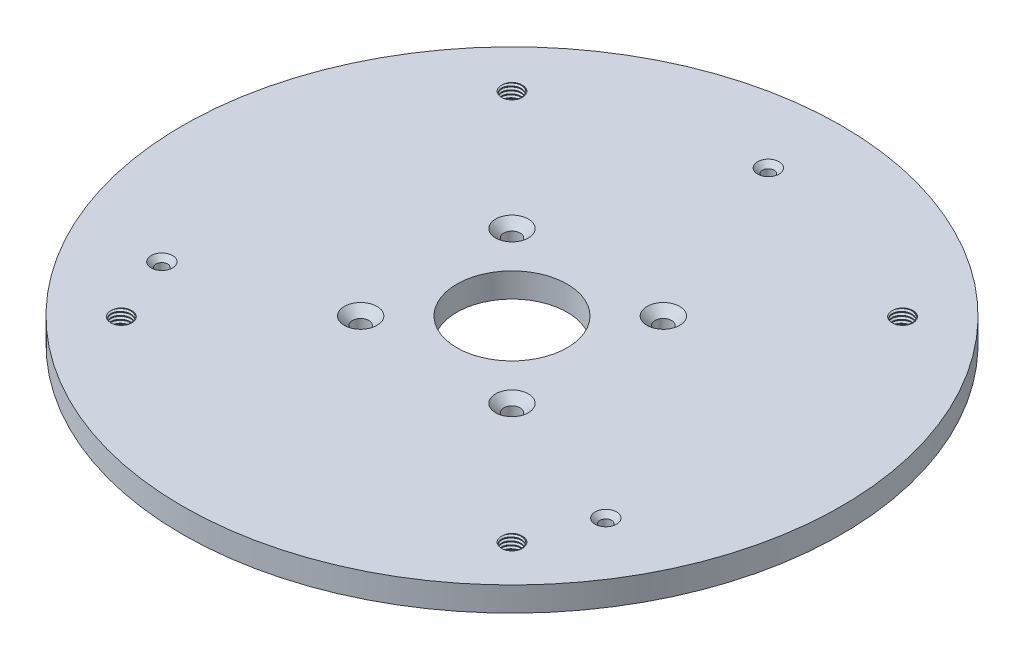
SolidWorks part; units mm, degrees
material "1060 Alloy"
ref_plane "Front Plane" through (0, 0, 0) normal (0, 0, 1) x (1, 0, 0)
ref_plane "Top Plane" through (0, 0, 0) normal (0, 1, 0) x (1, 0, 0)
ref_plane "Right Plane" through (0, 0, 0) normal (1, 0, 0) x (0, 0, -1)
sketch "Sketch1" plane through (0, 0, 0) normal (0, 1, 0) x (1, 0, 0)
  circle A0 centre (0, 0) radius 67.5
  dimension "D1" = 135
extrude "Boss-Extrude1" add sketch "Sketch1" along normal blind 5
hole_wizard "CSK for M3 SFHCS1" positions "Sketch3" profile "Sketch4" countersink size "M3" standard "ANSI Metric" end condition through all
sketch "Sketch3" plane through (0, 5, 0) normal (0, 1, 0) x (1, 0, 0)
  point P0 (-15.5, 15.5)
  point P7 (15.5, 15.5)
  point P8 (15.5, -15.5)
  point P9 (-15.5, -15.5)
  dimension "D3" = 15.5
  dimension "D4" = 15.5
  dimension "D5" = 31
  dimension "D6" = 31
  dimension "D1" = 2
  dimension "D2" = 2
sketch "Sketch4" plane through (-15.5, 5, -15.5) normal (1, 0, 0) x (0, 0, 1)
  line L0 (0, 0) -> (0, 5)
  line L1 (0, 5) -> (1.7, 5)
  line L2 (1.7, 5) -> (1.7, 1.66)
  line L3 (1.7, 1.66) -> (3.36, 0)
  line L5 (3.36, 0) -> (0, 0)
  line L6 (-1.7, 1.66) -> (-3.36, 0) construction
  line L11 (0, -6.35) -> (0, 107.95) construction
  dimension "Thru Hole Dia." = 3.4
  dimension "Thru Hole Depth" = 5
  dimension "Near C'Sink Dia." = 6.72
  dimension "Near C'Sink Angle" = 90
sketch "Sketch5" plane through (0, 5, 0) normal (0, 1, 0) x (1, 0, 0)
  circle A0 centre (0, 0) radius 11.3
  dimension "D1" = 22.6
extrude "Cut-Extrude1" cut sketch "Sketch5" against normal through all
hole_wizard "Ø4.0mm Dowel Hole1" positions "Sketch7" profile "Sketch8" hole size "Ø4.0" standard "AS"
sketch "Sketch7" plane through (0, 5, 0) normal (0, 1, 0) x (1, 0, 0)
  line L0 (40, 40) -> (-40, 40) construction
  line L1 (40, 40) -> (40, -40) construction
  point P0 (40, 40)
  point P5 (-40, 40)
  point P6 (-40, -40)
  point P7 (40, -40)
  dimension "D3" = 80
  dimension "D4" = 80
  dimension "D5" = 40
  dimension "D6" = 40
  dimension "D1" = 2
  dimension "D2" = 2
sketch "Sketch8" plane through (40, 5, -40) normal (1, 0, 0) x (0, 0, 1)
  line L0 (0, 0) -> (0, 16.2017)
  line L1 (0, 16.2017) -> (2, 15)
  line L2 (2, 15) -> (2, 0)
  line L5 (2, 0) -> (0, 0)
  line L10 (0, 16.2017) -> (-2, 15) construction
  line L11 (0, -6.35) -> (0, 107.95) construction
  dimension "Hole Dia." = 4
  dimension "Hole Depth" = 15
  dimension "Drill Angle" = 118
thread "Thread1" pitch 0.7 method cut trim with start face yes profile "Thread Profile2" start angle 1, offset 0.7, length 0, pitch 0.7, diameter 4
ref_plane "Plane2" through (-41.9997, 5.7, 39.9651) normal (-0.0175, 0, 0.9998) x (-0.9998, 0, -0.0175)
sketch "Thread Profile2" plane through (-41.9997, 5.7, 39.9651) normal (-0.0175, 0, 0.9998) x (-0.9998, 0, -0.0175)
  line L0 (0, 0) -> (0, 0.7) construction
  line L1 (0, 0) -> (0.3789, 0.2187)
  line L2 (0.3789, 0.2187) -> (0.3789, 0.3062)
  line L3 (0.3789, 0.3062) -> (0, 0.525)
  line L4 (0.3789, 0.2625) -> (0, 0.2625) construction
  line L11 (0, 0) -> (0, 0.525)
  point P2 (0, 0)
  dimension "Pitch" = 0.7
  dimension "Profile_Angle" = 60
  dimension "Profile_Land" = 0.0875
  dimension "Profile_Height" = 0.3789
thread "Thread2" pitch 0.7 method cut trim with start face yes profile "Thread Profile4" start angle 0, offset 0.7, length 0, pitch 0.7, diameter 4
ref_plane "Plane4" through (38, 5.7, 40) normal (0, 0, 1) x (-1, 0, 0)
sketch "Thread Profile4" plane through (38, 5.7, 40) normal (0, 0, 1) x (-1, 0, 0)
  line L0 (0, 0) -> (0, 0.7) construction
  line L1 (0, 0) -> (0.3789, 0.2187)
  line L2 (0.3789, 0.2187) -> (0.3789, 0.3062)
  line L3 (0.3789, 0.3062) -> (0, 0.525)
  line L4 (0.3789, 0.2625) -> (0, 0.2625) construction
  line L11 (0, 0) -> (0, 0.525)
  point P2 (0, 0)
  dimension "Pitch" = 0.7
  dimension "Profile_Angle" = 60
  dimension "Profile_Land" = 0.0875
  dimension "Profile_Height" = 0.3789
thread "Thread3" pitch 0.7 method cut trim with start face yes profile "Thread Profile5" start angle 0, offset 0.7, length 0, pitch 0.7, diameter 4
ref_plane "Plane5" through (38, 5.7, -40) normal (0, 0, 1) x (-1, 0, 0)
sketch "Thread Profile5" plane through (38, 5.7, -40) normal (0, 0, 1) x (-1, 0, 0)
  line L0 (0, 0) -> (0, 0.7) construction
  line L1 (0, 0) -> (0.3789, 0.2187)
  line L2 (0.3789, 0.2187) -> (0.3789, 0.3062)
  line L3 (0.3789, 0.3062) -> (0, 0.525)
  line L4 (0.3789, 0.2625) -> (0, 0.2625) construction
  line L11 (0, 0) -> (0, 0.525)
  point P2 (0, 0)
  dimension "Pitch" = 0.7
  dimension "Profile_Angle" = 60
  dimension "Profile_Land" = 0.0875
  dimension "Profile_Height" = 0.3789
thread "Thread4" pitch 0.7 method cut trim with start face yes profile "Thread Profile6" start angle 0, offset 0.7, length 0, pitch 0.7, diameter 4
ref_plane "Plane6" through (-42, 5.7, -40) normal (0, 0, 1) x (-1, 0, 0)
sketch "Thread Profile6" plane through (-42, 5.7, -40) normal (0, 0, 1) x (-1, 0, 0)
  line L0 (0, 0) -> (0, 0.7) construction
  line L1 (0, 0) -> (0.3789, 0.2187)
  line L2 (0.3789, 0.2187) -> (0.3789, 0.3062)
  line L3 (0.3789, 0.3062) -> (0, 0.525)
  line L4 (0.3789, 0.2625) -> (0, 0.2625) construction
  line L11 (0, 0) -> (0, 0.525)
  point P2 (0, 0)
  dimension "Pitch" = 0.7
  dimension "Profile_Angle" = 60
  dimension "Profile_Land" = 0.0875
  dimension "Profile_Height" = 0.3789
hole_wizard "CSK for M2 Countersunk Flat Head Screw1" positions "Sketch26" profile "Sketch28" countersink size "M2" standard "DIN" end condition through all
sketch "Sketch26" plane through (0, 5, 0) normal (0, 1, 0) x (1, 0, 0)
  line L0 (0, 0) -> (0, 67.5) construction
  line L2 (0, 0) -> (45.4663, -26.25) construction
  line L3 (45.4663, -26.25) -> (58.4567, -33.75) construction
  circle A0 centre (0, 0) radius 67.5 construction
  point P0 (0, 52.5)
  point P6 (45.4663, -26.25)
  point P7 (-45.4663, -26.25)
  dimension "D2" = 15
  dimension "D3" = 15
  dimension "D4" = 120
  dimension "D1" = 3
sketch "Sketch28" plane through (0, 5, -52.5) normal (1, 0, 0) x (0, 0, 1)
  line L0 (0, 0) -> (0, 5.2528)
  line L1 (0, 5.2528) -> (1.2, 5.2528)
  line L2 (1.2, 5.2528) -> (1.2, 1)
  line L3 (1.2, 1) -> (2.2, 0)
  line L5 (2.2, 0) -> (0, 0)
  line L6 (-1.2, 1) -> (-2.2, 0) construction
  line L11 (0, -6.35) -> (0, 107.95) construction
  dimension "Thru Hole Dia." = 2.4
  dimension "Thru Hole Depth" = 5.2528
  dimension "Near C'Sink Dia." = 4.4
  dimension "Near C'Sink Angle" = 90
equation "\"Test\"= 123"
